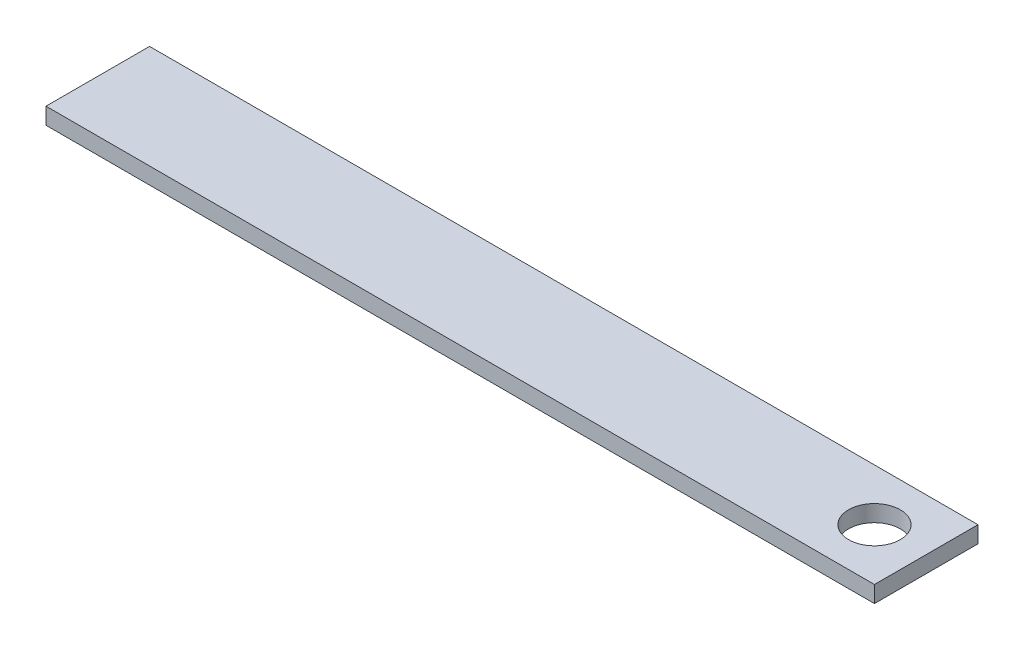
SolidWorks part; units mm, degrees
ref_plane "Front Plane" through (0, 0, 0) normal (0, 0, 1) x (1, 0, 0)
ref_plane "Top Plane" through (0, 0, 0) normal (0, 1, 0) x (1, 0, 0)
ref_plane "Right Plane" through (0, 0, 0) normal (1, 0, 0) x (0, 0, -1)
sketch "Sketch1" plane through (0, 0, 0) normal (0, 1, 0) x (1, 0, 0)
  line L1 (-100, 12.5) -> (100, 12.5)
  line L2 (-100, 12.5) -> (-100, -12.5)
  line L3 (-100, -12.5) -> (100, -12.5)
  line L4 (100, 12.5) -> (100, -12.5)
  line L5 (-100, 12.5) -> (100, -12.5) construction
  line L6 (-100, -12.5) -> (100, 12.5) construction
  circle A4 centre (87.5, 0) radius 6.25
  point P0 (0, 0)
  point P17 (100, 0)
  dimension "D3" = 12.5
  dimension "D4" = 12.5
  dimension "D1" = 25
  dimension "D2" = 200
extrude "Boss-Extrude1" add sketch "Sketch1" along normal blind 4 contours L3 L4 L1 L2 A4 | L3 region at (-2.2016, 0, 0)
